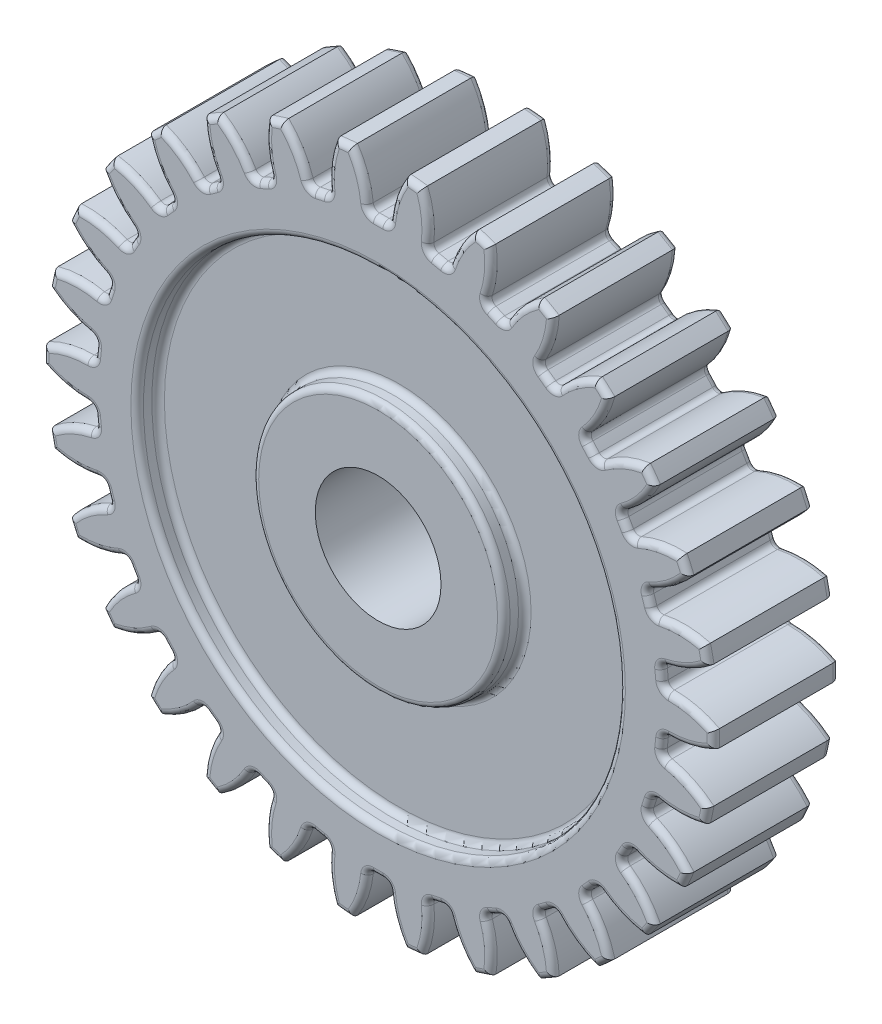
SolidWorks part; units mm, degrees
material "1023 Carbon Steel Sheet (SS)"
ref_plane "Front Plane" through (0, 0, 0) normal (0, 0, 1) x (1, 0, 0)
ref_plane "Top Plane" through (0, 0, 0) normal (0, 1, 0) x (1, 0, 0)
ref_plane "Right Plane" through (0, 0, 0) normal (1, 0, 0) x (0, 0, -1)
sketch "skBase" plane through (0, 0, 0) normal (0, 0, 1) x (1, 0, 0)
  circle A0 centre (0, 0) radius 15
  circle A1 centre (0, 0) radius 16
  circle A2 centre (0, 0) radius 13.6
  dimension "D1" = 30
  dimension "D3" = 2.4
extrude "Base" add sketch "skBase" along normal mid plane 15 contours A1
sketch "skToothProfile" plane through (0, 0, 0) normal (0, 0, 1) x (1, 0, 0)
  line L0 (0, 0) -> (0, 16) construction
  line L1 (-0.785, 14.9794) -> (0.785, 14.9794) construction
  line L2 (-0.513, 13.5903) -> (0, 0) construction
  line L3 (0, 12.8226) -> (-1.4964, 16.934) construction
  line L4 (0, 0) -> (1.6725, 15.9124) construction
  line L5 (0.785, 14.9794) -> (2.3465, 14.8153) construction
  circle A0 centre (0, 0) radius 16 construction
  arc A1 (-0.513, 13.5903) -> (-2.0888, 16.8712) centre (-5.0747, 13.4181) ccw
  arc A2 (0.513, 13.5903) -> (2.0888, 16.8712) centre (5.0747, 13.4181) cw
  circle A3 centre (0, 0) radius 13.6 construction
  arc A4 (0.513, 13.5903) -> (-0.513, 13.5903) centre (0, 0) ccw
  circle A5 centre (0, 0) radius 15 construction
  circle A6 centre (0, 0) radius 16 construction
  circle A7 centre (0, 0) radius 17
  arc A8 (2.0888, 16.8712) -> (-2.0888, 16.8712) centre (0, 0) ccw
  dimension "D2" = 20
  dimension "D3" = 6
extrude "ToothProfile" cut sketch "skToothProfile" against normal through all and the other way through all
fillet "FilletToothProfile" radius 0.3 2 edges at (0.513, 13.5903, 0) (-0.513, 13.5903, 0)
pattern_circular "CirPatternTeeth" count 30 over 360 about axis through (0, 0, 0) along (0, 0, 1) of "ToothProfile", "FilletToothProfile"
sketch "skChaveta" plane through (0, 0, 7.5) normal (0, 0, 1) x (1, 0, 0)
  line L0 (0, 5) -> (0, 0) construction
  line L2 (-1.5, 6) -> (1.5, 6)
  line L3 (-1.5, 6) -> (-1.5, 3)
  line L4 (-1.5, 3) -> (1.5, 3)
  line L5 (1.5, 6) -> (1.5, 3)
  line L6 (-1.5, 6) -> (1.5, 3) construction
  line L7 (-1.5, 3) -> (1.5, 6) construction
  circle A0 centre (0, 0) radius 5
  point P4 (0, 4.5)
  dimension "D1" = 10
  dimension "D2" = 8
  dimension "D3" = 3
  dimension "D4" = 3
extrude "Chaveta" cut sketch "skChaveta" against normal through all contours L2 L5 L4 L3 | A0
sketch "skRebaixo" plane through (0, 0, 7.5) normal (0, 0, 1) x (1, 0, 0)
  circle A0 centre (0, 0) radius 12.5
  circle A1 centre (0, 0) radius 7.5
  dimension "D1" = 25
  dimension "D2" = 15
extrude "Rebaixo" cut sketch "skRebaixo" against normal blind 3
mirror "MirrorRebaixo" about plane through (0, 0, 0) normal (0, 0, 1) of "Rebaixo"
fillet "FilletAcabamento" radius 0.2 6 edges at (1.6725, -15.9124, -7.5) (8, -13.8564, -7.5) (9.872, -9.4715, -7.5) (-3.2665, 13.2852, 7.5) (-12.5629, -8.1493, 7.5) (-12.871, 4.6373, 7.5)
sketch "skBalanceamento" plane through (0, 0, -4.5) normal (0, 0, -1) x (-1, 0, 0)
  line L0 (0, 0) -> (-10.8253, 6.25) construction
  line L1 (0, 0) -> (0, 12.3) construction
  line L2 (0, 0) -> (10.8253, 6.25) construction
  circle A0 centre (0, 0) radius 12.5 construction
  circle A1 centre (0, 0) radius 12.3 construction
  circle A2 centre (0, 0) radius 12.3 construction
  circle A3 centre (0, 0) radius 7.7 construction
  circle A4 centre (0, 0) radius 7.7 construction
  arc A5 (-8.6603, 5) -> (8.6603, 5) centre (0, 0) cw construction
  arc A6 (9.5263, 5.5) -> (-9.5263, 5.5) centre (0, 0) ccw
  arc A7 (7.7942, 4.5) -> (-7.7942, 4.5) centre (0, 0) ccw
  arc A8 (7.7942, 4.5) -> (9.5263, 5.5) centre (8.6603, 5) ccw
  arc A9 (-9.5263, 5.5) -> (-7.7942, 4.5) centre (-8.6603, 5) ccw
  point P15 (0, 10)
  dimension "D2" = 4.6
  dimension "D3" = 2.3
  dimension "D4" = 1
  dimension "D1" = 60
extrude "Balanceamento" cut sketch "skBalanceamento" against normal through all
chamfer "ChamferBalanceamento" distance 0.5 angle 45 8 edges at (-9.1603, 4.134, -4.5) (0, 11, -4.5) (0, 9, -4.5) (9.1603, 4.134, -4.5) (-9.1603, 4.134, 4.5) (0, 9, 4.5) (0, 11, 4.5) (9.1603, 4.134, 4.5)
mirror "MirrorBalanceamento" about plane through (0, 0, 0) normal (0, 1, 0) of "Balanceamento", "ChamferBalanceamento"
sketch "Sketch4" plane through (0, 0, -4.5) normal (0, 0, -1) x (-1, 0, 0)
  arc A0 (9.9593, 5.75) -> (-9.9593, 5.75) centre (0, 0) ccw construction
  arc A1 (9.9593, 5.75) -> (-9.9593, 5.75) centre (0, 0) ccw
  arc A2 (9.9593, -5.75) -> (7.3612, -4.25) centre (8.6603, -5) ccw construction
  arc A3 (-7.3612, -4.25) -> (7.3612, -4.25) centre (0, 0) ccw construction
  arc A4 (-9.9593, -5.75) -> (9.9593, -5.75) centre (0, 0) ccw construction
  arc A5 (-7.3612, -4.25) -> (-9.9593, -5.75) centre (-8.6603, -5) ccw construction
  arc A6 (7.3612, 4.25) -> (9.9593, 5.75) centre (8.6603, 5) ccw construction
  arc A7 (7.3612, 4.25) -> (-7.3612, 4.25) centre (0, 0) ccw construction
  arc A8 (-9.9593, 5.75) -> (-7.3612, 4.25) centre (-8.6603, 5) ccw construction
  arc A9 (9.9593, -5.75) -> (7.3612, -4.25) centre (8.6603, -5) ccw
  arc A10 (-7.3612, -4.25) -> (7.3612, -4.25) centre (0, 0) ccw
  arc A11 (-9.9593, -5.75) -> (9.9593, -5.75) centre (0, 0) ccw
  arc A12 (-7.3612, -4.25) -> (-9.9593, -5.75) centre (-8.6603, -5) ccw
  arc A13 (7.3612, 4.25) -> (9.9593, 5.75) centre (8.6603, 5) ccw
  arc A14 (7.3612, 4.25) -> (-7.3612, 4.25) centre (0, 0) ccw
  arc A15 (-9.9593, 5.75) -> (-7.3612, 4.25) centre (-8.6603, 5) ccw
extrude "Boss-Extrude1" add sketch "Sketch4" against normal up to surface (9 mm away) up to face at (0, -6.8505, 4.5)
sketch "Sketch5" plane through (0, 0, -7.5) normal (0, 0, -1) x (-1, 0, 0)
  line L0 (-2, 1.5) -> (2, 1.5)
  line L1 (-2.5, 0) -> (2.5, 0) construction
  line L2 (-2, -1.5) -> (2, -1.5)
  line L3 (1.7, 5.8) -> (1.7, 4.9143) construction
  line L4 (-1.3, 6.2) -> (1.3, 6.2) construction
  line L5 (-1.7, 4.9143) -> (-1.7, 5.8) construction
  line L6 (1.7, 5.8) -> (1.7, 4.9143)
  line L7 (-1.3, 6.2) -> (1.3, 6.2)
  line L8 (-1.7, 4.9143) -> (-1.7, 5.8)
  arc A0 (-2, 1.5) -> (-2, -1.5) centre (0, 0) ccw
  arc A1 (2, -1.5) -> (2, 1.5) centre (0, 0) ccw
  arc A2 (1.7, 5.8) -> (1.3, 6.2) centre (1.3, 5.8) ccw construction
  arc A3 (-1.3, 6.2) -> (-1.7, 5.8) centre (-1.3, 5.8) ccw construction
  arc A4 (-1.7, 4.9143) -> (1.7, 4.9143) centre (0, 0) ccw construction
  arc A5 (1.7, 5.8) -> (1.3, 6.2) centre (1.3, 5.8) ccw
  arc A6 (-1.3, 6.2) -> (-1.7, 5.8) centre (-1.3, 5.8) ccw
  arc A7 (-1.7, 4.9143) -> (1.7, 4.9143) centre (0, 0) ccw
  dimension "D1" = 1.5
  dimension "D2" = 5
extrude "Boss-Extrude2" add sketch "Sketch5" against normal up to surface (15 mm away) up to face at (0, 3.98, 7.5)
ref_plane "Plane1" through (0, 0, 3) normal (0, 0, 1) x (1, 0, 0)
sketch "Sketch6" plane through (0, 0, 3) normal (0, 0, 1) x (1, 0, 0)
  circle A0 centre (0, 0) radius 17.0521
extrude "Cut-Extrude1" cut sketch "Sketch6" along normal blind 10
ref_plane "Plane2" through (0, 0, -3) normal (0, 0, 1) x (1, 0, 0)
sketch "Sketch7" plane through (0, 0, -3) normal (0, 0, 1) x (1, 0, 0)
  circle A0 centre (0, 0) radius 17.4444
extrude "Cut-Extrude2" cut sketch "Sketch7" against normal blind 10
sketch "Sketch8" plane through (0, 0, -3) normal (0, 0, -1) x (-1, 0, 0)
  circle A0 centre (0, 0) radius 6
  circle A1 centre (0, 0) radius 11.5
extrude "Cut-Extrude3" cut sketch "Sketch8" against normal blind 1
mirror "Mirror1" about plane through (0, 0, 0) normal (0, 0, 1) of "Cut-Extrude3"
fillet "Fillet1" radius 0.3 8 edges at (-6, 0, -2) (-6, 0, -3) (-11.5, 0, -2) (-11.5, 0, -3) (-6, 0, 3) (-6, 0, 2) (-11.5, 0, 2) (-11.5, 0, 3)
fillet "Fillet2" radius 0.3 19 edges at (-14.7914, -2.3349, 3) (-12.9443, 9.4046, 3) (-2.4195, 13.4652, 3) (5.5316, 12.4242, 3) (9.4178, 11.6423, 3) (14.9536, -0.7914, 3) (14.7914, -2.3349, 3) (12.871, -4.6373, 3) (3.8683, -14.4663, 3) (-0.776, -14.9544, 3) (4.9443, -15.2169, -3) (15.6504, 3.3266, -3) (14.4623, 3.8831, -3) (5.9573, 12.3157, -3) (1.6725, 15.9124, -3) (-5.9573, 12.3157, -3) (-10.594, 10.5832, -3) (-14.4623, -3.8831, -3) (-7.6871, -11.317, -3)
sketch "Sketch9" plane through (0, 0, 3) normal (0, 0, 1) x (1, 0, 0)
  circle A0 centre (0, 0) radius 3
extrude "Cut-Extrude4" cut sketch "Sketch9" against normal through all
equation "\"Module\"= 1mm"
equation "\"Number_Of_Teeth\"= 30"
equation "\"D1@skBase\"=\"Module\" * \"Number_Of_Teeth\""
equation "\"D2@skBase\"=\"Module\""
equation "\"D3@skBase\"=\"Module\" * if( \"Module\" >=1.25, 2.25, 2.4)"
equation "\"Pressure_Angle\"= 20deg"
equation "\"D2@skToothProfile\"=\"Pressure_Angle\""
equation "\"D3@skToothProfile\"=180 / \"Number_Of_Teeth\""
equation "\"D1@FilletToothProfile\"= 0.3 * \"Module\""
equation "\"D1@CirPatternTeeth\"=\"Number_Of_Teeth\""
equation "\"Width\"= 15mm"
equation "\"D1@Base\"=\"Width\""
